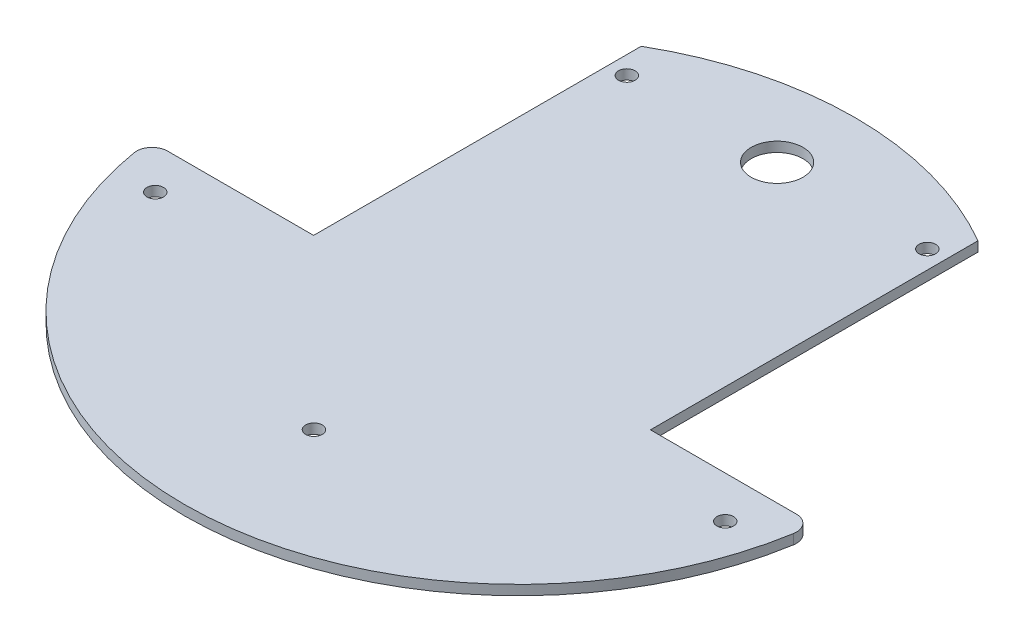
SolidWorks part; units mm, degrees
material "ABS"
ref_plane "Front Plane" through (0, 0, 0) normal (0, 0, 1) x (1, 0, 0)
ref_plane "Top Plane" through (0, 0, 0) normal (0, 1, 0) x (1, 0, 0)
ref_plane "Right Plane" through (0, 0, 0) normal (1, 0, 0) x (0, 0, -1)
sketch "Sketch1" plane through (0, 0, 0) normal (0, 1, 0) x (1, 0, 0)
  line L1 (-18, -10) -> (18, -10)
  line L2 (-18, -10) -> (-18, 10)
  line L3 (-18, 10) -> (18, 10)
  line L4 (18, -10) -> (18, 10)
  line L5 (-18, -10) -> (18, 10) construction
  line L6 (-18, 10) -> (18, -10) construction
  point P0 (0, 0)
  dimension "D1" = 36
  dimension "D2" = 20
extrude "Boss-Extrude1" add sketch "Sketch1" along normal blind 1.9
sketch "Sketch3" plane through (0, 0, 0) normal (0, -1, 0) x (1, 0, 0)
  line L0 (0, 0) -> (0, 52.1486) construction
  line L1 (37.5, -26.8695) -> (-37.5, -26.8695) construction
  line L2 (37.5, -26.8695) -> (32.5, -26.8695)
  line L3 (0, 0) -> (0, -36.2287) construction
  line L4 (-37.5, -26.8695) -> (-32.5, -26.8695)
  line L5 (32.5, -26.8695) -> (32.5, 33.1305)
  line L6 (-32.5, -26.8695) -> (-32.5, 33.1305)
  line L7 (32.5, 33.1305) -> (60.6723, 33.1305)
  line L9 (-32.5, 33.1305) -> (-60.6723, 33.1305)
  arc A0 (37.5, -26.8695) -> (-37.5, -26.8695) centre (0, 26.0743) cw
  arc A1 (-65.4068, -4.193) -> (-10.0124, -45.2973) centre (0, 26.0743) ccw construction
  arc A2 (68.1909, 19.5743) -> (-68.1909, 19.5743) centre (0, 26.0743) ccw construction
  arc A3 (63.6319, 36.621) -> (-63.6319, 36.621) centre (0, 26.0743) ccw
  circle A4 centre (0, 26.0743) radius 72.5 construction
  arc A5 (-60.6723, 33.1305) -> (-63.6319, 36.621) centre (-60.6723, 36.1305) cw
  arc A6 (60.6723, 33.1305) -> (63.6319, 36.621) centre (60.6723, 36.1305) ccw
  point P7 (0, 26.0743)
  point P20 (-64.1129, 33.1305)
  point P26 (64.1129, 33.1305)
  dimension "D1" = 4
  dimension "D3" = 5
  dimension "D4" = 60
  dimension "D5" = 3
  dimension "D6" = 7.0562
  dimension "D2" = 65
extrude "Boss-Extrude2" add sketch "Sketch3" against normal blind 1.9
sketch "Sketch4" plane through (0, 1.9, 0) normal (0, 1, 0) x (1, 0, 0)
  line L0 (-32.5, 26.8695) -> (-32.5, 34.1947)
  line L1 (-32.5, 34.1947) -> (-40.4421, 34.1947)
  line L2 (-40.4421, 34.1947) -> (-37.5, 26.8695)
  line L3 (-37.5, 26.8695) -> (-32.5, 26.8695)
  line L4 (0, 0) -> (0, 49.3906) construction
  line L5 (37.5, 26.8695) -> (32.5, 26.8695)
  line L6 (40.4421, 34.1947) -> (37.5, 26.8695)
  line L7 (32.5, 34.1947) -> (40.4421, 34.1947)
  line L8 (32.5, 26.8695) -> (32.5, 34.1947)
  arc A0 (37.5, 26.8695) -> (-37.5, 26.8695) centre (0, -26.0743) ccw construction
extrude "Cut-Extrude1" cut sketch "Sketch4" against normal blind 10
sketch "Sketch5" plane through (0, 1.9, 0) normal (0, 1, 0) x (1, 0, 0)
  line L0 (0, 0) -> (0, 38.8048) construction
  circle A0 centre (0, 23.8048) radius 5
  arc A1 (32.5, 30.0777) -> (-32.5, 30.0777) centre (0, -26.0743) ccw construction
  dimension "D1" = 10
  dimension "D2" = 15
extrude "Cut-Extrude2" cut sketch "Sketch5" against normal up to surface (1.9 mm away) up to face at (0, 0, 23.683)
sketch "Sketch6" plane through (0, 1.9, 0) normal (0, 1, 0) x (1, 0, 0)
  line L0 (0, 38.8048) -> (0, -90.5743) construction
  line L1 (-55, -41.1952) -> (55, -41.1952) construction
  line L2 (-29, 23.8048) -> (29, 23.8048) construction
  arc A0 (32.5, 30.0777) -> (-32.5, 30.0777) centre (0, -26.0743) ccw construction
  arc A1 (-63.6319, -36.621) -> (63.6319, -36.621) centre (0, -26.0743) ccw construction
  circle A2 centre (0, -65.5743) radius 1.6
  circle A3 centre (-55, -41.1952) radius 1.6
  circle A4 centre (55, -41.1952) radius 1.6
  circle A5 centre (-29, 23.8048) radius 1.6
  circle A6 centre (29, 23.8048) radius 1.6
  dimension "D1" = 25
  dimension "D2" = 3.2
  dimension "D3" = 55
  dimension "D5" = 58
  dimension "D4" = 80
  dimension "D6" = 65
extrude "Cut-Extrude3" cut sketch "Sketch6" against normal up to surface (1.9 mm away) up to face at (0, 0, -28.8048)
